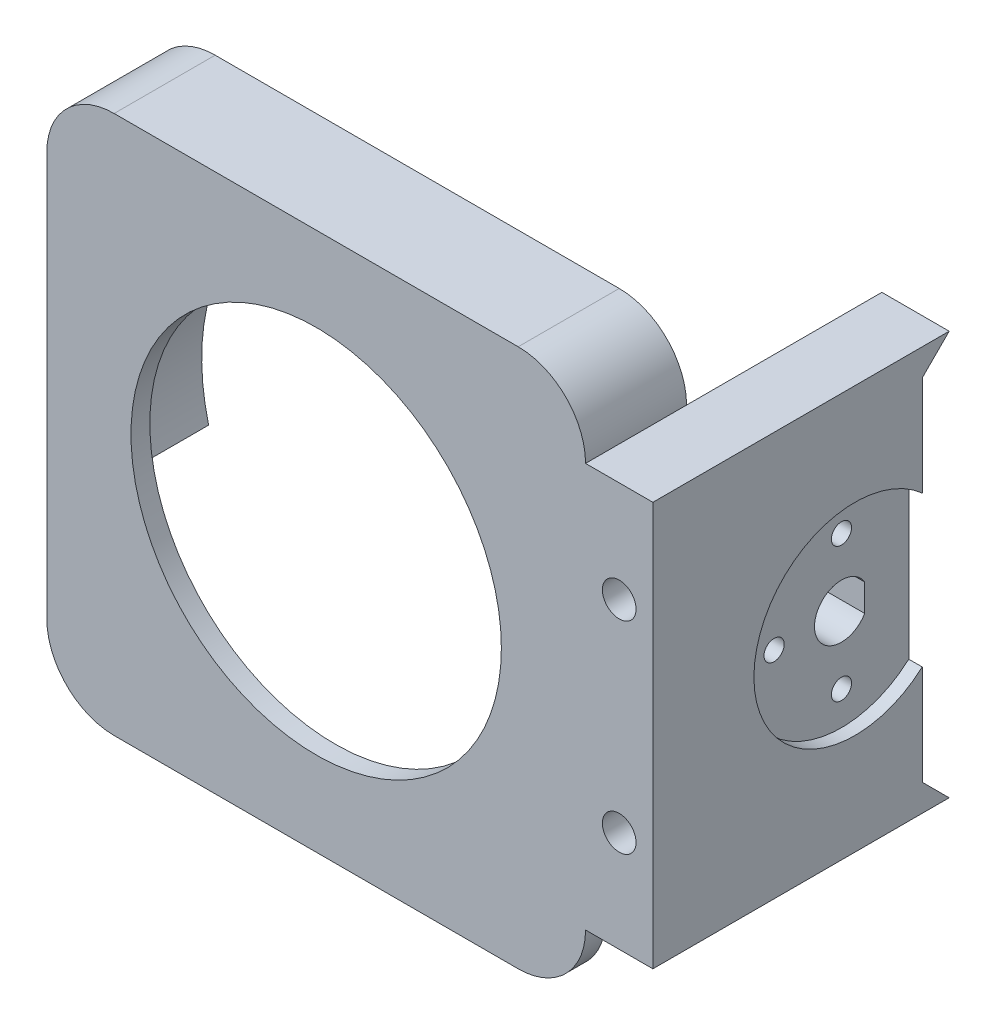
SolidWorks part; units mm, degrees
ref_plane "Front Plane" through (0, 0, 0) normal (0, 0, 1) x (1, 0, 0)
ref_plane "Top Plane" through (0, 0, 0) normal (0, 1, 0) x (1, 0, 0)
ref_plane "Right Plane" through (0, 0, 0) normal (1, 0, 0) x (0, 0, -1)
sketch "Sketch1" plane through (0, 0, 0) normal (0, 0, 1) x (1, 0, 0)
  line L1 (0, 0) -> (80, 0)
  line L2 (0, 0) -> (0, 80)
  line L3 (0, 80) -> (80, 80)
  line L4 (80, 0) -> (80, 80)
  circle A0 centre (40, 40) radius 32
  dimension "D3" = 64
  dimension "D1" = 80
  dimension "D2" = 80
extrude "Boss-Extrude1" add sketch "Sketch1" along normal blind 15
sketch "Sketch2" plane through (0, 0, 15) normal (0, 0, 1) x (1, 0, 0)
  circle A0 centre (40, 40) radius 32
  circle A1 centre (40, 40) radius 27.5
  dimension "D1" = 55
  dimension "D2" = 64
extrude "Boss-Extrude2" add sketch "Sketch2" against normal blind 2.8
fillet "Fillet1" radius 10 4 edges at (80, 0, 7.5) (0, 0, 7.5) (0, 80, 7.5) (80, 80, 7.5)
sketch "Sketch4" plane through (80, 0, 0) normal (1, 0, 0) x (0, 0, -1)
  line L1 (-15, 70) -> (25, 70)
  line L2 (-15, 70) -> (-15, 10)
  line L3 (-15, 10) -> (25, 10)
  line L4 (25, 70) -> (25, 10)
  dimension "D1" = 40
extrude "Boss-Extrude3" add sketch "Sketch4" along normal blind 10
sketch "Sketch10" plane through (0, 0, -25) normal (0, 0, -1) x (-1, 0, 0)
  line L0 (-90, 70) -> (-80, 70) construction
  line L1 (-90, 40) -> (-80, 40) construction
  line L2 (-90, 10) -> (-90, 70) construction
  line L3 (-80, 10) -> (-80, 70) construction
  circle A0 centre (-85, 55) radius 2.5
  circle A1 centre (-85, 25) radius 2.5
  dimension "D1" = 15
  dimension "D2" = 5
extrude "Cut-Extrude2" cut sketch "Sketch10" against normal through all
sketch "Sketch11" plane through (90, 0, 0) normal (1, 0, 0) x (0, 0, -1)
  line L0 (25, 70) -> (25, 66)
  line L1 (25, 10) -> (25, 70) construction
  line L2 (25, 66) -> (29, 70)
  line L3 (29, 70) -> (25, 70)
  line L4 (25, 40) -> (18.4514, 40) construction
  line L5 (25, 14) -> (29, 10)
  line L6 (25, 10) -> (25, 14)
  line L7 (29, 10) -> (25, 10)
  dimension "D1" = 4
  dimension "D2" = 4
extrude "Boss-Extrude7" add sketch "Sketch11" against normal blind 10
sketch "Sketch12" plane through (90, 0, 0) normal (1, 0, 0) x (0, 0, -1)
  line L0 (-15, 40) -> (15, 40) construction
  line L1 (-15, 70) -> (-15, 10) construction
  line L2 (18.4517, 42.0213) -> (18.4517, 37.9787)
  arc A0 (18.4517, 42.0213) -> (18.4517, 37.9787) centre (15, 40) ccw
  dimension "D2" = 8
  dimension "D1" = 30
extrude "Cut-Extrude3" cut sketch "Sketch12" against normal blind 10
sketch "Sketch13" plane through (90, 0, 0) normal (1, 0, 0) x (0, 0, -1)
  circle A0 centre (15, 40) radius 10
  circle A1 centre (15, 50) radius 1.5
  circle A3 centre (15, 40) radius 10
  circle A4 centre (15, 30) radius 1.5
  circle A5 centre (15, 40) radius 10
  circle A6 centre (5, 40) radius 1.5
  circle A7 centre (15, 40) radius 10
  arc A8 (24.925, 41.4981) -> (24.925, 38.5019) centre (25, 40) ccw [skipped]
  point P17 (15, 40)
  dimension "D1" = 20
  dimension "D2" = 3
  dimension "D3" = 4
extrude "Cut-Extrude5" cut sketch "Sketch13" against normal blind 30 contours A6 | A1 | A4
sketch "Sketch14" plane through (90, 0, 0) normal (1, 0, 0) x (0, 0, -1)
  circle A0 centre (15, 40) radius 15
  dimension "D1" = 30
extrude "Cut-Extrude6" cut sketch "Sketch14" against normal blind 2
sketch "Sketch16" plane through (0, 0, 0) normal (0, 0, -1) x (-1, 0, 0)
  line L1 (-70, 0) -> (-9.0323, 0)
  line L2 (-70, 0) -> (-70, 31.9378)
  line L3 (-70, 31.9378) -> (-9.0323, 31.9378)
  line L4 (-9.0323, 0) -> (-9.0323, 31.9378)
  circle A0 centre (-40, 40) radius 32 construction
extrude "Cut-Extrude10" cut sketch "Sketch16" against normal blind 12
sketch "Sketch17" plane through (0, 0, 0) normal (0, 0, -1) x (-1, 0, 0)
  line L1 (-80, 10) -> (0, 10)
  line L2 (-80, 10) -> (-80, 0)
  line L3 (-80, 0) -> (0, 0)
  line L4 (0, 10) -> (0, 0)
extrude "Cut-Extrude11" cut sketch "Sketch17" against normal blind 12
sketch "Sketch18" plane through (0, 10, 0) normal (0, -1, 0) x (1, 0, 0)
  circle A0 centre (5, 6) radius 2
  circle A1 centre (75, 6) radius 2
  dimension "D1" = 4
  dimension "D2" = 4
extrude "Cut-Extrude12" cut sketch "Sketch18" against normal blind 20
sketch "Sketch19" plane through (0, 30, 0) normal (0, -1, 0) x (1, 0, 0)
sketch "Sketch21" plane through (0, 0, 0) normal (0, 0, -1) x (-1, 0, 0)
  line L1 (-9.0323, 31.9378) -> (0, 31.9378)
  line L2 (-9.0323, 31.9378) -> (-9.0323, 0)
  line L3 (-9.0323, 0) -> (0, 0)
  line L4 (0, 31.9378) -> (0, 0)
  line L5 (-9.0323, 31.9378) -> (-80, 31.9378)
  line L6 (-9.0323, 31.9378) -> (-9.0323, 0)
  line L7 (-9.0323, 0) -> (-80, 0)
  line L8 (-80, 31.9378) -> (-80, 0)
extrude "Cut-Extrude14" cut sketch "Sketch21" against normal blind 12
